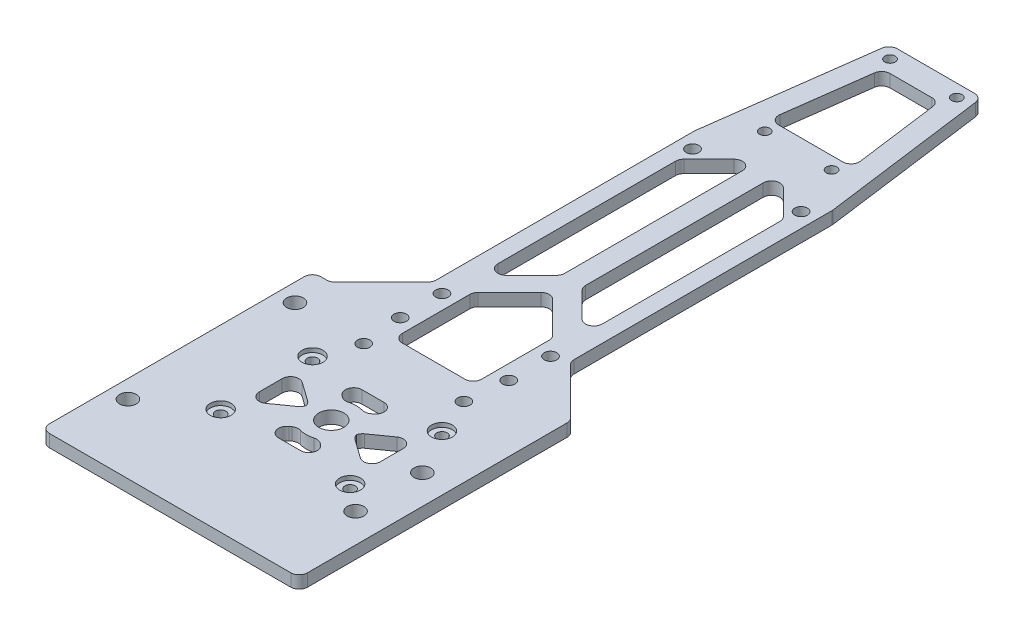
SolidWorks part; units mm, degrees
ref_plane "前视基准面" through (0, 0, 0) normal (0, 0, 1) x (1, 0, 0)
ref_plane "上视基准面" through (0, 0, 0) normal (0, 1, 0) x (1, 0, 0)
ref_plane "右视基准面" through (0, 0, 0) normal (1, 0, 0) x (0, 0, -1)
sketch "草图1" plane through (0, 0, 0) normal (0, 1, 0) x (1, 0, 0)
  line L0 (0, -120.3) -> (0, 0) construction
  line L1 (11, 0) -> (-11, 0)
  line L2 (-11, 0) -> (-16.5, -41.3)
  line L3 (-16.5, -41.3) -> (-16.5, -104)
  line L4 (-16.5, -120.3) -> (16.5, -120.3) construction
  line L5 (16.5, -41.3) -> (16.5, -104)
  line L6 (11, 0) -> (16.5, -41.3)
  line L7 (-8, -3) -> (-8, -33) construction
  line L8 (-16.5, -41.3) -> (0, -41.3) construction
  line L9 (-13, -45.3) -> (-13, -105.3) construction
  line L10 (-13, -105.3) -> (-13, -115.3) construction
  line L12 (28.8, -120.3) -> (28.8, -181.3)
  line L16 (0, -120.3) -> (0, -144.8) construction
  line L17 (0, -144.8) -> (28.8, -144.8) construction
  line L20 (16.5, -108) -> (28.8, -120.3) construction
  line L21 (16.5, -120.3) -> (28.8, -120.3) construction
  line L22 (-33, -116.3) -> (-33, -181.3)
  line L24 (28.8, -181.3) -> (-33, -181.3)
  line L25 (-16.5, -108) -> (-28.8, -120.3) construction
  line L26 (16.5, -108) -> (16.5, -120.3) construction
  line L29 (16.5, -104) -> (28.8, -116.3)
  line L31 (-16.5, -104) -> (-28.8, -116.3)
  line L32 (-28.8, -116.3) -> (-33, -116.3)
  line L33 (28.8, -120.3) -> (28.8, -116.3)
  line L34 (16.5, -108) -> (16.5, -104) construction
  line L35 (-16.5, -108) -> (-16.5, -104) construction
  line L36 (-28.8, -120.3) -> (-28.8, -116.3) construction
  circle A0 centre (-8, -3) radius 1.25
  circle A1 centre (-8, -33) radius 1.25
  circle A2 centre (8, -33) radius 1.25
  circle A3 centre (8, -3) radius 1.25
  circle A4 centre (-13, -45.3) radius 1.5
  circle A5 centre (-13, -105.3) radius 1.5
  circle A6 centre (-13, -115.3) radius 1.5
  circle A7 centre (13, -115.3) radius 1.5
  circle A8 centre (13, -105.3) radius 1.5
  circle A9 centre (13, -45.3) radius 1.5
  dimension "D2" = 2.5
  dimension "D3" = 8.3
  dimension "D5" = 16
  dimension "D6" = 3
  dimension "D7" = 3
  dimension "D10" = 4
  dimension "D11" = 3
  dimension "D12" = 26
  dimension "D13" = 5
  dimension "D17" = 45
  dimension "D18" = 135
  dimension "D19" = 33
  dimension "D20" = 4
  dimension "D1" = 33
  dimension "D4" = 30
  dimension "D8" = 79
  dimension "D9" = 10
  dimension "D14" = 24.5
  dimension "D15" = 28.8
  dimension "D16" = 61
extrude "凸台-拉伸1" add sketch "草图1" along normal blind 3
sketch "草图2" plane through (0, 3, 0) normal (0, 1, 0) x (1, 0, 0)
  line L0 (0, 0) -> (0, -181.3) construction
  line L1 (-33, -181.3) -> (28.8, -181.3) construction
  line L2 (6.7549, -6) -> (-6.7549, -6)
  line L3 (-6.7549, -6) -> (-9.951, -30)
  line L4 (-9.951, -30) -> (9.951, -30)
  line L5 (6.7549, -6) -> (9.951, -30)
  line L6 (11, 0) -> (-11, 0) construction
  line L7 (16.5, -41.3) -> (11, 0) construction
  line L8 (12.5, -97.2289) -> (2.5, -87.2289)
  line L9 (-12.5, -49.0426) -> (-2.5, -39.0426)
  line L10 (-12.5, -49.0426) -> (-12.5, -97.2289)
  line L11 (-12.5, -97.2289) -> (-2.5, -87.2289)
  line L12 (-2.5, -39.0426) -> (-2.5, -87.2289)
  line L13 (2.5, -39.0426) -> (2.5, -87.2289)
  line L14 (12.5, -49.0426) -> (2.5, -39.0426)
  line L15 (12.5, -49.0426) -> (12.5, -97.2289)
  line L16 (-16.5, -41.3) -> (-16.5, -104) construction
  line L17 (-9.5, -101.3) -> (0, -91.8)
  line L19 (-9.5, -101.3) -> (-9.5, -120.3)
  line L20 (-9.5, -120.3) -> (9.5, -120.3)
  line L21 (9.5, -101.3) -> (9.5, -120.3)
  line L23 (9.5, -101.3) -> (0, -91.8)
  line L24 (16.5, -104) -> (16.5, -41.3) construction
  circle A0 centre (8, -33) radius 1.25 construction
  circle A2 centre (-13, -45.3) radius 1.5 construction
  circle A3 centre (13, -105.3) radius 1.5 construction
  circle A4 centre (13, -115.3) radius 1.5 construction
  point P10 (0, -30)
  point P11 (0, -6)
  dimension "D9" = 3
  dimension "D1" = 6
  dimension "D2" = 5
  dimension "D3" = 3
  dimension "D4" = 4
  dimension "D5" = 45
  dimension "D6" = 5
  dimension "D7" = 7
  dimension "D8" = 5
  dimension "D10" = 45
  dimension "D11" = 4
  dimension "D12" = 5
extrude "切除-拉伸1" cut sketch "草图2" against normal blind 10
fillet "圆角1" radius 2 28 edges at (-9.5, 1.5, 120.3) (9.5, 1.5, 120.3) (12.5, 1.5, 97.2289) (2.5, 1.5, 87.2289) (-2.5, 1.5, 87.2289) (-12.5, 1.5, 97.2289) (-9.5, 1.5, 101.3) (9.5, 1.5, 101.3) (0, 1.5, 91.8) (12.5, 1.5, 49.0426) (-12.5, 1.5, 49.0426) (-2.5, 1.5, 39.0426) (2.5, 1.5, 39.0426) (9.951, 1.5, 30) (-9.951, 1.5, 30) (6.7549, 1.5, 6) (-6.7549, 1.5, 6) (11, 1.5, 0) (-11, 1.5, 0) (28.8, 1.5, 181.3) (-16.5, 1.5, 41.3) (16.5, 1.5, 41.3) (-33, 1.5, 181.3) (16.5, 1.5, 104) (28.8, 1.5, 116.3) (-28.8, 1.5, 116.3) (-16.5, 1.5, 104) (-33, 1.5, 116.3)
sketch "草图3" plane through (0, 0, 0) normal (0, -1, 0) x (1, 0, 0)
  line L0 (-28.7, 164.8) -> (-28.7, 124.8) construction
  line L1 (-31, 181.3) -> (26.8, 181.3) construction
  line L2 (-33, 118.3) -> (-33, 179.3) construction
  line L3 (21.8, 160.8) -> (21.8, 144.8) construction
  line L4 (28.8, 179.3) -> (28.8, 117.1284) construction
  circle A0 centre (-28.7, 164.8) radius 2
  circle A1 centre (-28.7, 124.8) radius 2
  circle A2 centre (21.8, 160.8) radius 2
  circle A3 centre (21.8, 144.8) radius 2
  dimension "D2" = 4
  dimension "D6" = 4
  dimension "D1" = 40
  dimension "D3" = 16.5
  dimension "D4" = 4.3
  dimension "D5" = 16
  dimension "D7" = 7
  dimension "D8" = 20.5
extrude "切除-拉伸2" cut sketch "草图3" against normal through all
sketch "草图5" plane through (0, 3, 0) normal (0, 1, 0) x (1, 0, 0)
  line L10 (0, 0) -> (0, -181.3) construction
  line L11 (-31, -181.3) -> (26.8, -181.3) construction
  line L21 (-28.7, -144.8) -> (0, -144.8) construction
  line L31 (-28.7, -124.8) -> (-28.7, -164.8) construction
  line L33 (-15.5, -133.8) -> (15.5, -133.8) construction
  line L34 (-15.5, -133.8) -> (-15.5, -155.8) construction
  line L35 (-15.5, -155.8) -> (15.5, -155.8) construction
  line L36 (15.5, -133.8) -> (15.5, -155.8) construction
  line L37 (-15.5, -133.8) -> (15.5, -155.8) construction
  line L38 (-15.5, -155.8) -> (15.5, -133.8) construction
  circle A0 centre (15.5, -133.8) radius 1.25
  circle A1 centre (-15.5, -133.8) radius 1.25
  circle A2 centre (-15.5, -155.8) radius 1.25
  circle A3 centre (15.5, -155.8) radius 1.25
  point P21 (0, 0)
  dimension "D3" = 2.5
  dimension "D1" = 31
  dimension "D2" = 22
extrude "切除-拉伸3" cut sketch "草图5" against normal through all
sketch "草图6" plane through (0, 3, 0) normal (0, 1, 0) x (1, 0, 0)
  line L16 (15.5, -133.8) -> (-15.5, -155.8) construction
  line L17 (-15.5, -133.8) -> (15.5, -155.8) construction
  line L18 (-15.5, -133.8) -> (15.5, -133.8) construction
  line L19 (-15.5, -133.8) -> (-15.5, -155.8) construction
  line L20 (-15.5, -155.8) -> (15.5, -155.8) construction
  line L21 (15.5, -155.8) -> (15.5, -133.8) construction
  line L22 (-14.5, -134.8) -> (-14.5, -154.8)
  line L23 (-14.5, -154.8) -> (14.5, -154.8)
  line L24 (14.5, -154.8) -> (14.5, -134.8)
  line L25 (-14.5, -134.8) -> (14.5, -134.8)
  line L26 (13.7638, -131.3535) -> (-17.2362, -153.3535)
  line L27 (17.2362, -136.2465) -> (-13.7638, -158.2465)
  line L28 (-17.2362, -136.2465) -> (13.7638, -158.2465)
  line L29 (-13.7638, -131.3535) -> (17.2362, -153.3535)
  circle A0 centre (0, -144.8) radius 3
  circle A1 centre (0, -144.8) radius 6
  dimension "D1" = 6
  dimension "D2" = 3
  dimension "D6" = 3
  dimension "D3" = 1
  dimension "D4" = 3
  dimension "D5" = 3
  dimension "D7" = 3
extrude "切除-拉伸4" cut sketch "草图6" against normal blind 10 contours A1 L26 L25 L29 | A1 L29 L24 L27 | A1 L27 L23 L28 | A1 L28 L22 L26 | A0 region at (-11.4375, 3, 144.8) region at (0, 3, 136.5565) region at (0, 3, 153.0435) region at (0, 3, 144.8) region at (11.4375, 3, 144.8)
sketch "草图7" plane through (0, 3, 0) normal (0, 1, 0) x (1, 0, 0)
  circle A2 centre (15.5, -133.8) radius 2.5
  circle A3 centre (-15.5, -133.8) radius 2.5
  circle A4 centre (-15.5, -155.8) radius 2.5
  circle A7 centre (15.5, -155.8) radius 2.5
  dimension "D2" = 5
extrude "切除-拉伸5" cut sketch "草图7" against normal blind 1
fillet "圆角2" radius 2 16 edges at (8.9073, 1.5, 154.8) (-8.9073, 1.5, 154.8) (-2.5013, 1.5, 150.2538) (2.5013, 1.5, 150.2538) (14.5, 1.5, 138.1884) (14.5, 1.5, 151.4116) (5.9737, 1.5, 145.3607) (5.9737, 1.5, 144.2393) (-14.5, 1.5, 151.4116) (-5.9737, 1.5, 144.2393) (-5.9737, 1.5, 145.3607) (-8.9073, 1.5, 134.8) (8.9073, 1.5, 134.8) (2.5013, 1.5, 139.3462) (-2.5013, 1.5, 139.3462) (-14.5, 1.5, 138.1884)
sketch "草图8" plane through (0, 3, 0) normal (0, 1, 0) x (1, 0, 0)
  line L0 (12, -125.05) -> (-12, -125.05) construction
  line L1 (0, -120.3) -> (0, -125.05) construction
  line L2 (-7.5, -120.3) -> (7.5, -120.3) construction
  circle A0 centre (12, -125.05) radius 1.5
  circle A1 centre (-12, -125.05) radius 1.5
  dimension "D3" = 3
  dimension "D1" = 24
  dimension "D2" = 4.75
extrude "切除-拉伸6" cut sketch "草图8" against normal blind 10
